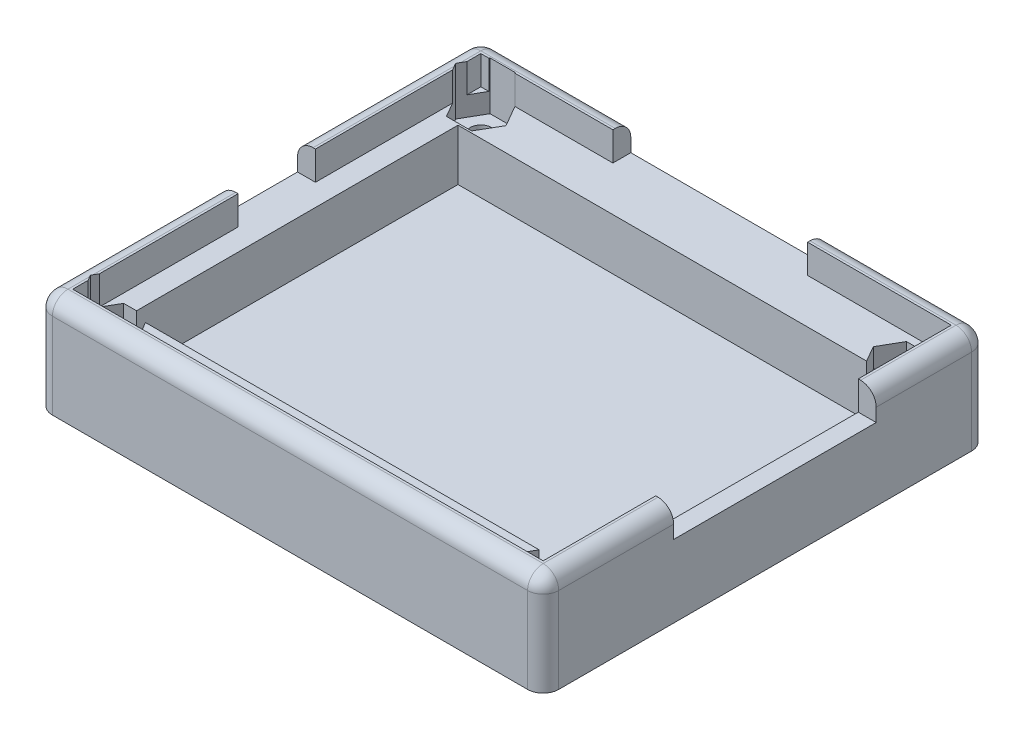
SolidWorks part; units mm, degrees
ref_plane "Front Plane" through (0, 0, 0) normal (0, 0, 1) x (1, 0, 0)
ref_plane "Top Plane" through (0, 0, 0) normal (0, 1, 0) x (1, 0, 0)
ref_plane "Right Plane" through (0, 0, 0) normal (1, 0, 0) x (0, 0, -1)
sketch "Sketch1" plane through (0, 0, 0) normal (0, 1, 0) x (1, 0, 0)
  line L0 (-41.275, 36.195) -> (41.275, 36.195)
  line L1 (-38.1, 33.02) -> (38.1, 33.02) construction
  line L2 (-38.1, 33.02) -> (-38.1, -33.02) construction
  line L3 (-38.1, -33.02) -> (38.1, -33.02) construction
  line L4 (38.1, 33.02) -> (38.1, -33.02) construction
  line L5 (-38.1, 33.02) -> (38.1, -33.02) construction
  line L6 (-38.1, -33.02) -> (38.1, 33.02) construction
  line L7 (41.275, 36.195) -> (41.275, -36.195)
  line L8 (-41.275, -36.195) -> (41.275, -36.195)
  line L9 (-41.275, 36.195) -> (-41.275, -36.195)
  point P0 (0, 0)
  dimension "D1" = 76.2
  dimension "D2" = 66.04
  dimension "D3" = 3.175
extrude "Boss-Extrude1" add sketch "Sketch1" along normal blind 16.51
sketch "Sketch3" plane through (0, 16.51, 0) normal (0, 1, 0) x (1, 0, 0)
  line L0 (-38.354, 33.274) -> (38.354, 33.274)
  line L1 (-38.1, 33.02) -> (38.1, 33.02) construction
  line L2 (-38.1, 33.02) -> (-38.1, -33.02) construction
  line L3 (-38.1, -33.02) -> (38.1, -33.02) construction
  line L4 (38.1, 33.02) -> (38.1, -33.02) construction
  line L5 (-38.1, 33.02) -> (38.1, -33.02) construction
  line L6 (-38.1, -33.02) -> (38.1, 33.02) construction
  line L7 (38.354, 33.274) -> (38.354, -33.274)
  line L8 (-38.354, -33.274) -> (38.354, -33.274)
  line L9 (-38.354, 33.274) -> (-38.354, -33.274)
  point P0 (0, 0)
  dimension "D1" = 76.2
  dimension "D2" = 66.04
  dimension "D3" = 0.254
extrude "Cut-Extrude1" cut sketch "Sketch3" against normal blind 4.699
hole_wizard "#4 Clearance Hole1" positions "Sketch7" profile "Sketch6" hole size "#4" standard "ANSI Inch"
sketch "Sketch7" plane through (0, 11.811, 0) normal (0, 1, 0) x (1, 0, 0)
  line L1 (-38.1, 33.02) -> (38.1, 33.02) construction
  line L2 (-38.1, 33.02) -> (-38.1, -33.02) construction
  line L3 (-38.1, -33.02) -> (38.1, -33.02) construction
  line L4 (38.1, 33.02) -> (38.1, -33.02) construction
  line L5 (-38.1, 33.02) -> (38.1, -33.02) construction
  line L6 (-38.1, -33.02) -> (38.1, 33.02) construction
  point P0 (-34.925, 29.845)
  point P2 (34.29, 28.575)
  point P4 (34.29, -29.845)
  point P6 (-34.925, -29.845)
  dimension "D1" = 76.2
  dimension "D2" = 66.04
  dimension "D3" = 3.175
  dimension "D4" = 62.865
  dimension "D5" = 3.175
  dimension "D6" = 3.175
  dimension "D7" = 3.175
  dimension "D8" = 72.39
  dimension "D9" = 72.39
  dimension "D10" = 61.595
sketch "Sketch6" plane through (-34.925, 11.811, -29.845) normal (1, 0, 0) x (0, 0, 1)
  line L0 (0, 0) -> (0, 11.1978)
  line L1 (0, 11.1978) -> (1.7272, 10.16)
  line L2 (1.7272, 10.16) -> (1.7272, 0)
  line L5 (1.7272, 0) -> (0, 0)
  line L10 (0, 11.1978) -> (-1.7272, 10.16) construction
  line L11 (0, -6.35) -> (0, 107.95) construction
  dimension "Hole Dia." = 3.4544
  dimension "Hole Depth" = 10.16
  dimension "Drill Angle" = 118
sketch "Sketch8" plane through (0, 11.811, 0) normal (0, 1, 0) x (1, 0, 0)
  line L0 (38.2495, -29.845) -> (36.2697, -26.416)
  line L1 (-31.1122, 29.845) -> (-33.0186, 33.147) construction
  line L2 (-33.0186, 33.147) -> (-36.8314, 33.147) construction
  line L3 (-36.8314, 33.147) -> (-38.7378, 29.845) construction
  line L4 (-38.7378, 29.845) -> (-36.8314, 26.543) construction
  line L5 (-36.8314, 26.543) -> (-33.0186, 26.543) construction
  line L6 (-33.0186, 26.543) -> (-31.1122, 29.845) construction
  line L7 (37.9562, 28.575) -> (36.1231, 31.75) construction
  line L8 (36.1231, 31.75) -> (32.4569, 31.75) construction
  line L9 (32.4569, 31.75) -> (30.6238, 28.575) construction
  line L10 (30.6238, 28.575) -> (32.4569, 25.4) construction
  line L11 (32.4569, 25.4) -> (36.1231, 25.4) construction
  line L12 (36.1231, 25.4) -> (37.9562, 28.575) construction
  line L13 (-31.2588, -29.845) -> (-33.0919, -26.67) construction
  line L14 (-33.0919, -26.67) -> (-36.7581, -26.67) construction
  line L15 (-36.7581, -26.67) -> (-38.5912, -29.845) construction
  line L16 (-38.5912, -29.845) -> (-36.7581, -33.02) construction
  line L17 (-36.7581, -33.02) -> (-33.0919, -33.02) construction
  line L18 (-33.0919, -33.02) -> (-31.2588, -29.845) construction
  line L19 (37.9562, -29.845) -> (36.1231, -26.67) construction
  line L20 (36.1231, -26.67) -> (32.4569, -26.67) construction
  line L21 (32.4569, -26.67) -> (30.6238, -29.845) construction
  line L22 (30.6238, -29.845) -> (32.4569, -33.02) construction
  line L23 (32.4569, -33.02) -> (36.1231, -33.02) construction
  line L24 (36.1231, -33.02) -> (37.9562, -29.845) construction
  line L25 (36.2697, -26.416) -> (32.3103, -26.416)
  line L26 (32.3103, -26.416) -> (30.3305, -29.845)
  line L27 (30.3305, -29.845) -> (32.3103, -33.274)
  line L28 (32.3103, -33.274) -> (36.2697, -33.274)
  line L29 (36.2697, -33.274) -> (38.2495, -29.845)
  line L30 (-30.8189, 29.845) -> (-32.8719, 33.401)
  line L31 (-32.8719, 33.401) -> (-36.9781, 33.401)
  line L32 (-36.9781, 33.401) -> (-39.0311, 29.845)
  line L33 (-39.0311, 29.845) -> (-36.9781, 26.289)
  line L34 (-36.9781, 26.289) -> (-32.8719, 26.289)
  line L35 (-32.8719, 26.289) -> (-30.8189, 29.845)
  line L36 (38.2495, 28.575) -> (36.2697, 32.004)
  line L37 (36.2697, 32.004) -> (32.3103, 32.004)
  line L38 (32.3103, 32.004) -> (30.3305, 28.575)
  line L39 (30.3305, 28.575) -> (32.3103, 25.146)
  line L40 (32.3103, 25.146) -> (36.2697, 25.146)
  line L41 (36.2697, 25.146) -> (38.2495, 28.575)
  line L42 (-30.9655, -29.845) -> (-32.9453, -26.416)
  line L43 (-32.9453, -26.416) -> (-36.9047, -26.416)
  line L44 (-36.9047, -26.416) -> (-38.8845, -29.845)
  line L45 (-38.8845, -29.845) -> (-36.9047, -33.274)
  line L46 (-36.9047, -33.274) -> (-32.9453, -33.274)
  line L47 (-32.9453, -33.274) -> (-30.9655, -29.845)
  circle A0 centre (-34.925, 29.845) radius 3.302 construction
  circle A1 centre (34.29, 28.575) radius 3.175 construction
  circle A2 centre (-34.925, -29.845) radius 3.175 construction
  circle A3 centre (34.29, -29.845) radius 3.175 construction
  dimension "D1" = 0.254
  dimension "D2" = 0.254
  dimension "D3" = 0.254
  dimension "D4" = 0.254
extrude "Cut-Extrude2" cut sketch "Sketch8" against normal blind 3.175 and the other way blind 8.255
sketch "Sketch9" plane through (0, 11.811, 0) normal (0, 1, 0) x (1, 0, 0)
  line L0 (38.354, -33.274) -> (38.354, 33.274) construction
  line L1 (-34.7997, 25.9941) -> (38.354, 25.9941)
  line L2 (-34.7997, 25.9941) -> (-34.7997, -27.3459)
  line L3 (-34.7997, -27.3459) -> (38.354, -27.3459)
  line L4 (38.354, 25.9941) -> (38.354, -27.3459)
  line L5 (-34.7997, 25.9941) -> (38.354, -27.3459) construction
  line L6 (-34.7997, -27.3459) -> (38.354, 25.9941) construction
  point P0 (1.7771, -0.6759)
  dimension "D1" = 53.34
extrude "Cut-Extrude3" cut sketch "Sketch9" against normal blind 8.382
sketch "Sketch12" plane through (0, 16.51, 0) normal (0, 1, 0) x (1, 0, 0)
  line L0 (38.1, 1.5875) -> (24.0608, 1.5875) construction
  line L1 (-38.1, 33.02) -> (38.1, 33.02) construction
  line L2 (-38.1, 33.02) -> (-38.1, -33.02) construction
  line L3 (-38.1, -33.02) -> (38.1, -33.02) construction
  line L4 (38.1, 33.02) -> (38.1, -33.02) construction
  line L5 (-38.1, 33.02) -> (38.1, -33.02) construction
  line L6 (-38.1, -33.02) -> (38.1, 33.02) construction
  line L7 (-41.275, 6.3059) -> (-41.275, -6.3059)
  line L8 (-41.275, 6.3059) -> (-30.4454, 6.3059)
  line L9 (41.275, 18.1012) -> (41.275, -14.9262)
  line L10 (-41.275, -6.3059) -> (-30.4454, -6.3059)
  line L11 (-30.4454, 6.3059) -> (-30.4454, -6.3059)
  line L12 (41.275, 18.1012) -> (24.0608, 18.1012)
  line L13 (-34.925, 0) -> (-30.4454, 0) construction
  line L14 (-41.275, 36.195) -> (-41.275, -36.195) construction
  line L15 (41.275, -14.9262) -> (24.0608, -14.9262)
  line L16 (24.0608, 18.1012) -> (24.0608, -14.9262)
  line L17 (41.275, 36.195) -> (-41.275, 36.195) construction
  line L18 (-16.8275, 16.51) -> (14.9225, 16.51)
  line L19 (41.275, -36.195) -> (41.275, 36.195) construction
  line L20 (-16.8275, 16.51) -> (-16.8275, 36.195)
  line L21 (-16.8275, 36.195) -> (14.9225, 36.195)
  line L22 (14.9225, 16.51) -> (14.9225, 36.195)
  point P0 (0, 0)
  point P6 (-34.925, 0)
  point P7 (33.655, 10.795)
  point P8 (-9.525, 20.32)
  point P9 (6.35, 24.13)
  point P10 (33.655, -7.62)
  point P11 (33.655, 1.5875)
  point P15 (33.655, 1.5875)
  point P29 (-16.8275, 16.51)
  point P30 (14.9225, 33.02)
  point P37 (-34.925, 29.845)
  point P38 (34.29, 28.575)
  point P40 (34.29, -29.845)
  point P42 (-34.925, -29.845)
  dimension "D1" = 76.2
  dimension "D2" = 66.04
  dimension "D3" = 3.175
  dimension "D4" = 33.02
  dimension "D5" = 28.575
  dimension "D6" = 53.34
  dimension "D7" = 57.15
  dimension "D8" = 44.45
  dimension "D9" = 71.755
  dimension "D10" = 43.815
  dimension "D11" = 25.4
  dimension "D12" = 71.755
  dimension "D13" = 71.755
  dimension "D14" = 34.6075
  dimension "D15" = 21.2725
  dimension "D16" = 49.53
  dimension "D17" = 53.0225
  dimension "D18" = 66.04
extrude "Cut-Extrude8" cut sketch "Sketch12" against normal up to surface (4.699 mm away) up to face at (-2.0136, 11.811, -18.8835)
fillet "Fillet1" radius 2.54 11 edges at (41.275, 16.51, 25.5606) (41.275, 8.255, -36.195) (41.275, 16.51, -27.1481) (28.0987, 16.51, -36.195) (-29.0513, 16.51, -36.195) (-41.275, 16.51, -21.2504) (-41.275, 16.51, 21.2504) (0, 16.51, 36.195) (41.275, 8.255, 36.195) (-41.275, 8.255, 36.195) (-41.275, 8.255, -36.195)
